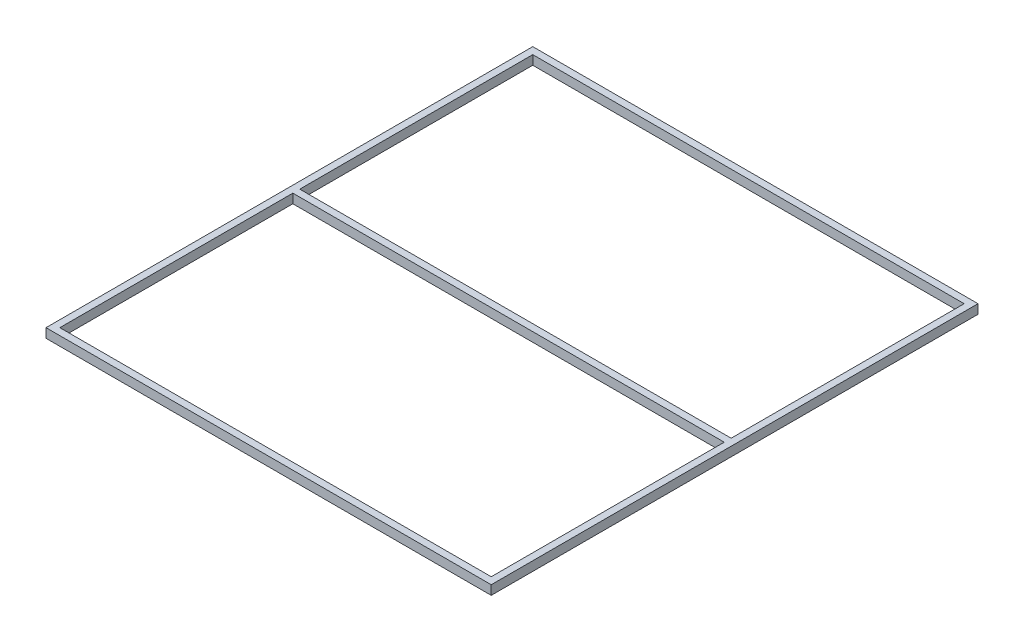
SolidWorks part; units mm, degrees
ref_plane "Front Plane" through (0, 0, 0) normal (0, 0, 1) x (1, 0, 0)
ref_plane "Top Plane" through (0, 0, 0) normal (0, 1, 0) x (1, 0, 0)
ref_plane "Right Plane" through (0, 0, 0) normal (1, 0, 0) x (0, 0, -1)
other "Configuration Table"
sketch "MetalBase" plane through (0, 0, 0) normal (0, 1, 0) x (1, 0, 0)
  line L0 (-60, -60) -> (7660, -60)
  line L1 (0, 0) -> (7600, 0)
  line L2 (0, 0) -> (0, 2020)
  line L3 (0, 4100) -> (7600, 4100)
  line L4 (7600, 0) -> (7600, 2020)
  line L5 (7660, -60) -> (7660, 4160)
  line L6 (-60, 4160) -> (7660, 4160)
  line L7 (-60, -60) -> (-60, 4160)
  line L8 (0, 2050) -> (7600, 2050) construction
  line L9 (0, 2020) -> (7600, 2020)
  line L10 (0, 2080) -> (7600, 2080)
  line L11 (0, 2080) -> (0, 4100)
  line L12 (7600, 2080) -> (7600, 4100)
  line L13 (0, 0) -> (0, 4100) construction
  line L15 (7600, 0) -> (7600, 4100) construction
  point P15 (7660, 2050)
  dimension "D1" = 4100
  dimension "D2" = 7600
  dimension "D6" = 4220
  dimension "D7" = 7720
  dimension "D3" = 60
  dimension "D4" = 30
  dimension "D5" = 30
sketch "InternalSpace" plane through (0, 0, 0) normal (0, 1, 0) x (1, 0, 0)
  line L26 (50, 50) -> (7550, 50)
  line L27 (7550, 50) -> (7550, 4050)
  line L28 (7550, 4050) -> (50, 4050)
  line L29 (50, 4050) -> (50, 50)
  line L30 (50, 50) -> (7550, 50)
  line L31 (7550, 50) -> (7550, 4050)
  line L32 (7550, 4050) -> (50, 4050)
  line L33 (50, 4050) -> (50, 50)
  dimension "D2" = 4000
  dimension "D3" = 7500
  dimension "D1" = 110
sketch "Furniture" plane through (0, 0, 0) normal (0, 1, 0) x (1, 0, 0)
  line L0 (6750, 2050) -> (6750, 4050)
  line L1 (2200, 2550) -> (1400, 2550)
  line L2 (2200, 2550) -> (2200, 4050)
  line L3 (2200, 4050) -> (1400, 4050)
  line L4 (1400, 2550) -> (1400, 4050)
  line L5 (1050, 50) -> (50, 50)
  line L6 (1050, 50) -> (1050, 2050)
  line L7 (1050, 2050) -> (50, 2050)
  line L8 (50, 50) -> (50, 2050)
  line L9 (6350, 2110) -> (7550, 2110)
  line L10 (2200, 4050) -> (2200, 150)
  line L11 (0, 0) -> (7600, 0) construction
  line L12 (6350, 50) -> (6350, 2110)
  line L13 (6470, 50) -> (6470, 1990)
  line L15 (2200, 2050) -> (7550, 2050) construction
  line L17 (1979.5569, 919.0285) -> (2200, 150)
  line L18 (6350, 150) -> (5722.0427, 459.305)
  line L19 (6710, 1120.0467) -> (7310, 1120.0467)
  line L24 (6710, 1120.0467) -> (6710, 1880.0467)
  line L25 (6710, 1880.0467) -> (7310, 1880.0467)
  line L26 (7310, 1120.0467) -> (7310, 1880.0467)
  line L27 (6350, 2110) -> (5750, 2110)
  line L28 (6350, 2110) -> (6350, 1510)
  line L29 (6350, 1510) -> (5750, 1510)
  line L30 (5750, 2110) -> (5750, 1510)
  line L31 (2320, 2050) -> (4320, 2050) construction
  line L32 (4320, 2050) -> (4320, 4050) construction
  line L33 (2200, 150) -> (2499.3532, 150) construction
  line L34 (2499.3532, 150) -> (2499.3532, 981.1813) construction
  line L35 (2499.3532, 981.1813) -> (2200, 981.1813) construction
  line L36 (2320, 4050) -> (2320, 150)
  line L37 (2200, 150) -> (2200, 50)
  line L38 (50, 50) -> (7550, 50) construction
  line L39 (2320, 150) -> (2320, 50)
  line L40 (7550, 4050) -> (50, 4050) construction
  line L41 (7550, 50) -> (7550, 4050) construction
  line L42 (50, 4050) -> (50, 50) construction
  line L43 (7550, 4050) -> (50, 4050) construction
  line L44 (7550, 50) -> (7550, 4050) construction
  line L45 (50, 50) -> (7550, 50) construction
  line L46 (50, 4050) -> (50, 50) construction
  line L47 (7010, 1120.0467) -> (7010, 1445.9123) construction
  line L48 (6470, 1990) -> (7550, 1990)
  line L49 (-60, -60) -> (-60, 4160) construction
  line L50 (7550, 809.8905) -> (7383.7397, 809.8905)
  line L51 (7550, 809.8905) -> (7550, 230.8186)
  line L52 (7550, 230.8186) -> (7383.7397, 230.8186)
  line L53 (7283.7397, 709.8905) -> (7283.7397, 330.8186)
  line L54 (7660, 4160) -> (-60, 4160) construction
  line L55 (-60, 4160) -> (-60, -60) construction
  line L56 (-60, -60) -> (7660, -60) construction
  line L57 (7660, -60) -> (7660, 4160) construction
  arc A1 (1979.5569, 919.0285) -> (1414.1883, 0) centre (2200, 150) ccw construction
  arc A2 (5722.0427, 459.305) -> (6350, 850) centre (6350, 150) cw construction
  arc A3 (7383.7397, 230.8186) -> (7283.7397, 330.8186) centre (7383.7397, 330.8186) cw
  arc A4 (7383.7397, 809.8905) -> (7283.7397, 709.8905) centre (7383.7397, 709.8905) ccw
  point P56 (7010, 1990)
  dimension "D13" = 600
  dimension "D21" = 100
  dimension "D1" = 1500
  dimension "D2" = 800
  dimension "D3" = 2000
  dimension "D4" = 1000
  dimension "D5" = 100
  dimension "D6" = 60
  dimension "D7" = 700
  dimension "D8" = 600
  dimension "D9" = 2260
  dimension "D10" = 800
  dimension "D11" = 100
  dimension "D12" = 760
  dimension "D14" = 2000
  dimension "D15" = 800
  dimension "D16" = 2000
  dimension "D17" = 600
  dimension "D18" = 60
  dimension "D19" = 4150
  dimension "D20" = 120
  dimension "D22" = 120
  dimension "D23" = 110
  dimension "D25" = 4220
  dimension "D26" = 1200
  dimension "D27" = 4030
  dimension "D24" = 110
sketch "Metal frame" plane through (0, 0, 0) normal (0, 1, 0) x (1, 0, 0)
  line L0 (0, 4100) -> (7600, 4100) construction
  line L1 (0, 4100) -> (7600, 4100)
  line L3 (0, 0) -> (0, 2020)
  line L4 (0, 0) -> (7600, 0) construction
  line L5 (0, 0) -> (7600, 0)
  line L7 (7600, 0) -> (7600, 2020)
  line L8 (-60, 4160) -> (7660, 4160)
  line L9 (7660, -60) -> (7660, 4160)
  line L10 (-60, -60) -> (7660, -60)
  line L11 (-60, -60) -> (-60, 4160)
  line L12 (0, 2050) -> (62.1159, 2050) construction
  line L13 (7600, 2080) -> (0, 2080)
  line L15 (7600, 2020) -> (0, 2020)
  line L17 (7600, 2080) -> (7600, 4100)
  line L18 (0, 2080) -> (0, 4100)
  line L19 (7600, 0) -> (7600, 4100) construction
  line L21 (0, 0) -> (0, 4100) construction
  point P14 (-60, 2050)
  dimension "D2" = 7720
  dimension "D3" = 4220
  dimension "D4" = 60
  dimension "D1" = 60
sketch "Walls bottom" plane through (0, 0, 0) normal (0, 1, 0) x (1, 0, 0)
  line L0 (-60, 4160) -> (7660, 4160) construction
  line L2 (-60, -60) -> (7660, -60) construction
  line L3 (7660, -60) -> (7660, 4160) construction
  line L4 (-60, -60) -> (-60, 4160) construction
  line L5 (-60, -60) -> (7660, -60)
  line L6 (7660, -60) -> (7660, 4160)
  line L7 (-60, 4160) -> (7660, 4160)
  line L8 (-60, -60) -> (-60, 4160)
  line L9 (40, 40) -> (40, 4060)
  line L10 (40, 4060) -> (7560, 4060)
  line L11 (7560, 40) -> (7560, 4060)
  line L12 (40, 40) -> (7560, 40)
  dimension "D2" = 4020
  dimension "D3" = 7520
  dimension "D4" = 7720
  dimension "D5" = 4220
  dimension "D1" = 100
sketch "Sketch15" plane through (0, 0, 0) normal (0, 1, 0) x (1, 0, 0)
  line L2 (7550, 50) -> (5502.4266, 50)
  line L3 (7550, 50) -> (7550, 1250)
  line L4 (7550, 1250) -> (5502.4266, 1250)
  line L5 (5502.4266, 50) -> (5502.4266, 1250)
  dimension "D1" = 1200
extrude "MetalFrame" add sketch "Metal frame" against normal blind 80 contours L11 L10 L9 L8 L15 L7 L5 L3 L13 L18 L1 L17 region at (3800, 0, -2050)
sketch "Sketch18" plane through (0, 0, 0) normal (0, 1, 0) x (1, 0, 0)
  line L0 (0, 0) -> (7600, 0) construction
  line L1 (3800, -1014.8769) -> (8467.9433, -1014.8769)
  line L2 (3800, -1014.8769) -> (3800, 5493.3133)
  line L3 (3800, 5493.3133) -> (8467.9433, 5493.3133)
  line L4 (8467.9433, -1014.8769) -> (8467.9433, 5493.3133)
  point P6 (3800, 0)
extrude "Cut-Extrude1" cut sketch "Sketch18" against normal through all
sketch "Sketch19" plane through (0, 0, 0) normal (0, 1, 0) x (1, 0, 0)
  line L0 (0, 0) -> (3800, 0) construction
  line L1 (3800, 4100) -> (3740, 4100)
  line L2 (3800, 4100) -> (3800, 0)
  line L3 (3800, 0) -> (3740, 0)
  line L4 (3740, 4100) -> (3740, 0)
  dimension "D1" = 60
extrude "Boss-Extrude1" add sketch "Sketch19" against normal blind 80
sketch "Sketch20" plane through (0, 0, 0) normal (1, 0, 0) x (0, 0, -1)
  line L0 (2050, 0) -> (2050, 2900) construction
  line L1 (4160, 0) -> (-60, 0) construction
  line L2 (4160, 0) -> (4160, 2700) construction
  line L3 (4160, 2700) -> (2050, 2900) construction
  line L4 (2050, 2900) -> (5424.8088, 2900) construction
  line L5 (4160, 2700) -> (4439.2907, 2673.5269) construction
  dimension "D1" = 2700
  dimension "D2" = 2900
  dimension "D4" = 2119.4575
  dimension "D5" = 2400
  dimension "D6" = 280.5425
